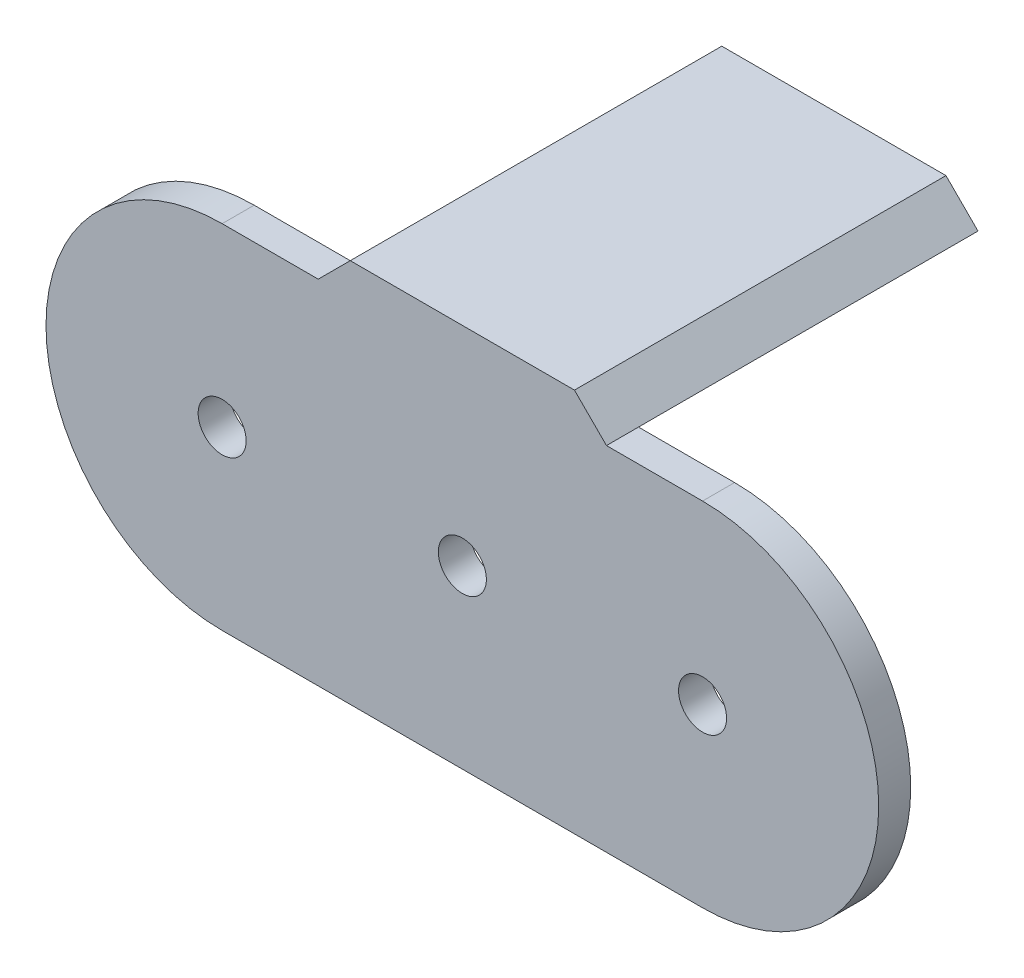
SolidWorks part; units mm, degrees
ref_plane "Front Plane" through (0, 0, 0) normal (0, 0, 1) x (1, 0, 0)
ref_plane "Top Plane" through (0, 0, 0) normal (0, 1, 0) x (1, 0, 0)
ref_plane "Right Plane" through (0, 0, 0) normal (1, 0, 0) x (0, 0, -1)
sketch "Sketch1" plane through (0, 0, 0) normal (0, 0, 1) x (1, 0, 0)
  line L0 (-15, 0) -> (15, 0) construction
  line L1 (-15, 11) -> (15, 11)
  line L2 (-15, -11) -> (15, -11)
  arc A0 (-15, 11) -> (-15, -11) centre (-15, 0) ccw
  arc A1 (15, -11) -> (15, 11) centre (15, 0) ccw
  circle A2 centre (-15, 0) radius 1.5
  circle A3 centre (15, 0) radius 1.5
  circle A4 centre (0, 0) radius 1.5
  point P3 (0, 0)
  dimension "D2" = 11
  dimension "D3" = 3
  dimension "D1" = 30
extrude "Boss-Extrude1" add sketch "Sketch1" along normal blind 2
sketch "Sketch2" plane through (0, 11, 0) normal (0, 1, 0) x (1, 0, 0)
  line L2 (9, -2) -> (9, 21.2)
  line L3 (9, 21.2) -> (-9, 21.2)
  line L4 (-9, -2) -> (-9, 21.2)
  line L5 (9, -2) -> (-9, -2)
  line L6 (15, -2) -> (-15, -2) construction
  point P7 (0, -2)
  point P12 (0, -2)
  dimension "D1" = 18
  dimension "D2" = 23.2
extrude "Boss-Extrude2" add sketch "Sketch2" along normal blind 2
chamfer "Chamfer1" distance 2 angle 45 2 edges at (-9, 13, -9.6) (9, 13, -9.6)
